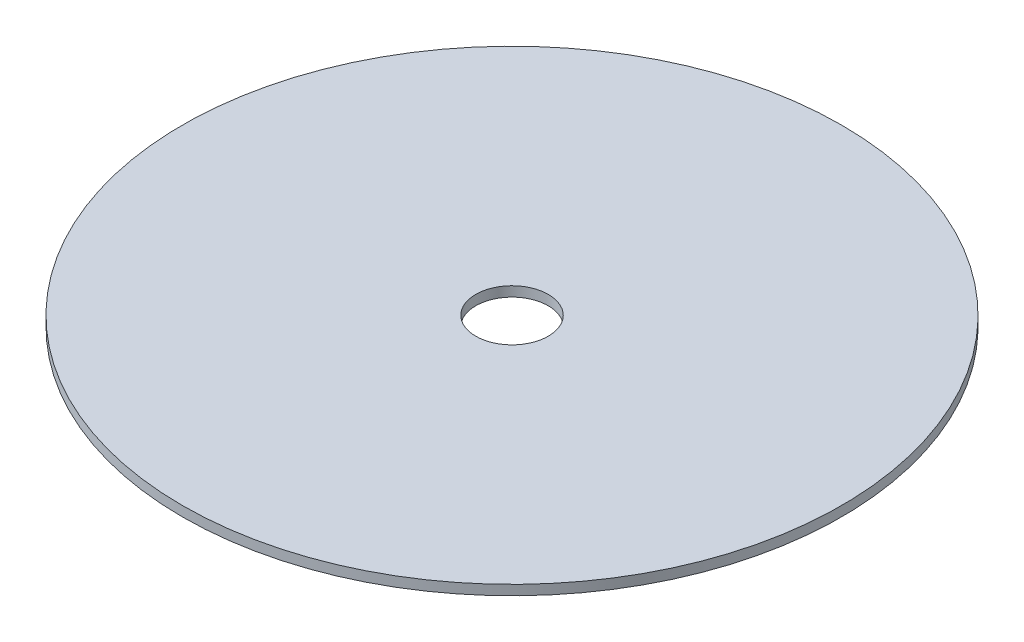
SolidWorks part; units mm, degrees
ref_plane "Front Plane" through (0, 0, 0) normal (0, 0, 1) x (1, 0, 0)
ref_plane "Top Plane" through (0, 0, 0) normal (0, 1, 0) x (1, 0, 0)
ref_plane "Right Plane" through (0, 0, 0) normal (1, 0, 0) x (0, 0, -1)
ref_axis "Axe1" through (0, 55, 0) along (0, -1, 0)
sketch "Esquisse2" plane through (0, 0, 0) normal (0, 0, 1) x (1, 0, 0)
  line L0 (0, 0) -> (100, 0)
  line L1 (100, 0) -> (100, 3)
  line L4 (100, 3) -> (0, 3)
  line L5 (0, 55) -> (0, -55) construction
  line L6 (0, 3) -> (0, 0)
  dimension "D1" = 100
  dimension "D3" = 3
revolve "MainRevolution" add sketch "Esquisse2" angle 360 about axis through (0, 55, 0) along (0, -1, 0)
sketch "Esquisse4" plane through (0, 3, 0) normal (0, 1, 0) x (1, 0, 0)
  circle A0 centre (0, 0) radius 11
  dimension "D1" = 22
extrude "Enlèv. mat.-Extru.6" cut sketch "Esquisse4" against normal through all
